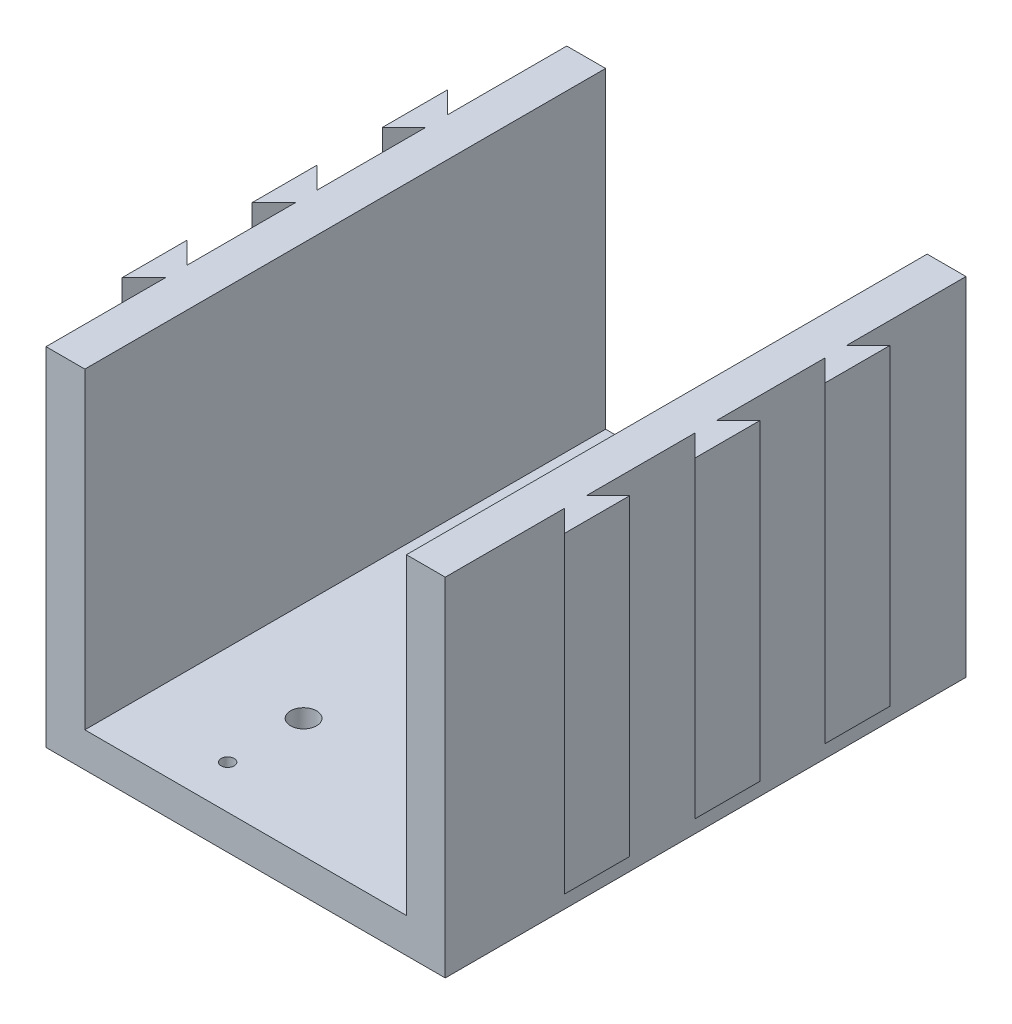
SolidWorks part; units mm, degrees
ref_plane "Front Plane" through (0, 0, 0) normal (0, 0, 1) x (1, 0, 0)
ref_plane "Top Plane" through (0, 0, 0) normal (0, 1, 0) x (1, 0, 0)
ref_plane "Right Plane" through (0, 0, 0) normal (1, 0, 0) x (0, 0, -1)
sketch "Sketch1" plane through (0, 0, 0) normal (0, 1, 0) x (1, 0, 0)
  line L1 (0, 0) -> (92, 0)
  line L2 (0, 0) -> (0, 120)
  line L3 (0, 120) -> (92, 120)
  line L4 (92, 0) -> (92, 120)
  dimension "D1" = 120
  dimension "D2" = 92
extrude "Boss-Extrude1" add sketch "Sketch1" along normal blind 8
sketch "Sketch2" plane through (0, 8, 0) normal (0, 1, 0) x (1, 0, 0)
  line L0 (0, 120) -> (8.9486, 120)
  line L1 (92, 120) -> (0, 120) construction
  line L2 (8.9486, 120) -> (8.9486, 0)
  line L3 (0, 0) -> (92, 0) construction
  line L4 (8.9486, 0) -> (0, 0)
  line L5 (0, 0) -> (0, 27.5)
  line L6 (0, 120) -> (0, 0) construction
  line L7 (0, 27.5) -> (-5, 22.5)
  line L8 (-5, 22.5) -> (-5, 37.5)
  line L9 (-5, 37.5) -> (0, 32.5)
  line L12 (-5, 52.5) -> (-5, 67.5)
  line L13 (-5, 67.5) -> (0, 62.5)
  line L14 (0, 62.5) -> (0, 87.5)
  line L15 (0, 87.5) -> (-5, 82.5)
  line L16 (-5, 82.5) -> (-5, 97.5)
  line L17 (-5, 97.5) -> (0, 92.5)
  line L18 (0, 92.5) -> (0, 120)
  line L19 (-5, 52.5) -> (0, 57.5)
  line L20 (0, 57.5) -> (0, 32.5)
  line L21 (46, 120) -> (46, 0) construction
  line L22 (92, 57.5) -> (92, 32.5)
  line L23 (97, 52.5) -> (92, 57.5)
  line L24 (92, 92.5) -> (92, 120)
  line L25 (97, 97.5) -> (92, 92.5)
  line L26 (97, 82.5) -> (97, 97.5)
  line L27 (92, 87.5) -> (97, 82.5)
  line L28 (92, 62.5) -> (92, 87.5)
  line L29 (97, 67.5) -> (92, 62.5)
  line L30 (97, 52.5) -> (97, 67.5)
  line L31 (97, 37.5) -> (92, 32.5)
  line L32 (97, 22.5) -> (97, 37.5)
  line L33 (92, 27.5) -> (97, 22.5)
  line L34 (92, 0) -> (92, 27.5)
  line L35 (83.0514, 0) -> (92, 0)
  line L36 (83.0514, 120) -> (83.0514, 0)
  line L37 (92, 120) -> (83.0514, 120)
  dimension "D1" = 27.5
  dimension "D2" = 5
  dimension "D3" = 45
  dimension "D4" = 25
  dimension "D5" = 5
  dimension "D6" = 25
  dimension "D7" = 27.5
  dimension "D8" = 5
  dimension "D9" = 5
  dimension "D10" = 5
  dimension "D11" = 45
  dimension "D12" = 45
  dimension "D13" = 45
extrude "Boss-Extrude2" add sketch "Sketch2" along normal blind 72
sketch "Sketch3" plane through (0, 0, 0) normal (0, -1, 0) x (1, 0, 0)
  line L0 (31.85, 0) -> (31.85, -120) construction
  line L1 (0, 0) -> (92, 0) construction
  line L2 (92, -120) -> (0, -120) construction
  line L3 (92, -92.5) -> (0, -92.5) construction
  line L4 (92, 0) -> (92, -120) construction
  line L5 (0, -120) -> (0, 0) construction
  line L6 (0, -60) -> (92, -60) construction
  line L7 (92, -57.5) -> (92, -62.5) construction
  circle A0 centre (31.85, -92.5) radius 3
  circle A1 centre (31.85, -110) radius 1.5
  circle A4 centre (31.85, -10) radius 1.5
  circle A5 centre (31.85, -27.5) radius 3
  dimension "D2" = 6
  dimension "D5" = 3
  dimension "D1" = 27.5
  dimension "D3" = 31.85
  dimension "D4" = 17.5
extrude "Cut-Extrude1" cut sketch "Sketch3" against normal up to next
